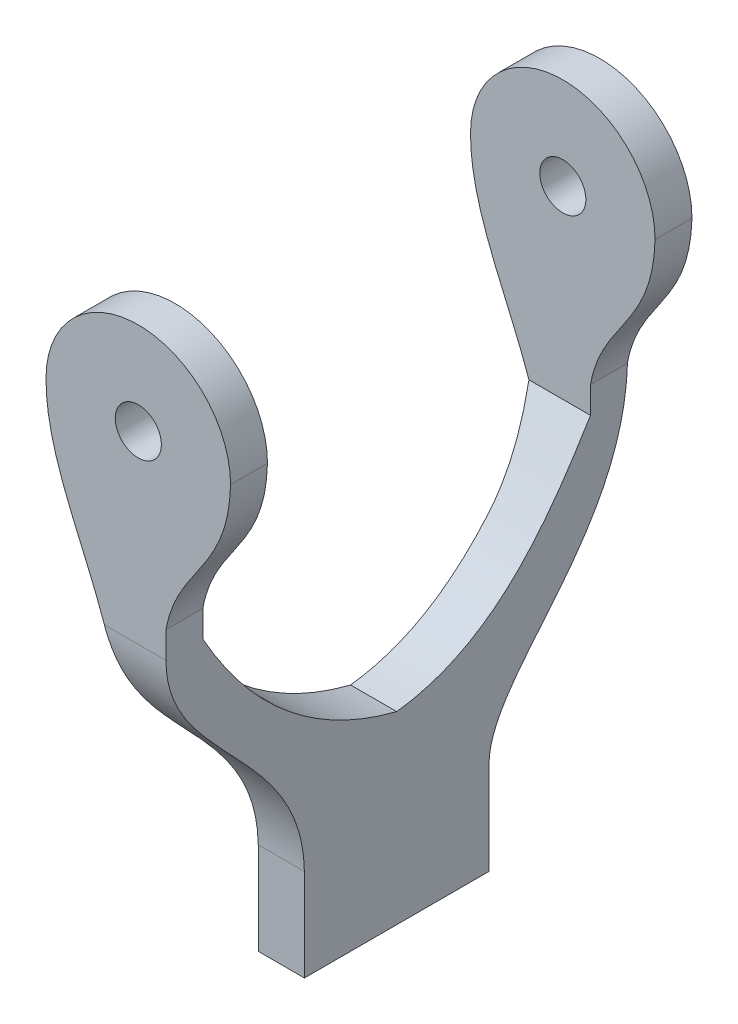
SolidWorks part; units mm, degrees
ref_plane "Plan de face" through (0, 0, 0) normal (0, 0, 1) x (1, 0, 0)
ref_plane "Plan de dessus" through (0, 0, 0) normal (0, 1, 0) x (1, 0, 0)
ref_plane "Plan de droite" through (0, 0, 0) normal (1, 0, 0) x (0, 0, -1)
sketch "Esquisse1" plane through (0, 0, 0) normal (0, 0, 1) x (1, 0, 0)
  line L0 (0, 0) -> (3, 0)
  line L2 (3, 0) -> (-2, 0)
  line L3 (3, 0) -> (3, -57.3)
  line L4 (3, -57.3) -> (-2, -57.3)
  line L5 (-2, 0) -> (-2, -57.3)
  circle A0 centre (0, 0) radius 10
  circle A1 centre (0, 0) radius 2.5
  spline S0 degree 3 poles (10, 0) (9.7605, -8.6814) (4.197, -10.3098) (3, -17.1257) knots 0 0 0 0 1 1 1 1
  spline S1 degree 3 poles (-10, 0) (-10.0381, -9.9152) (-2.1321, -18.0107) (-2, -28.65) knots 0 0 0 0 1 1 1 1
  dimension "D1" = 3
  dimension "D2" = 20
  dimension "D3" = 5
  dimension "D4" = 57.3
  dimension "D5" = 5
extrude "Boss.-Extru.1" add sketch "Esquisse1" along normal blind 50 contours A0 S1 L5 | A0 L5 L4 L3 | S0 A0 L3 | S0 A0 L5 A1 L2 L3 | A1 L5 A0 L3 L2 region at (-0.8796, 2.6387, 0) region at (0.5747, -5.836, 0) region at (5.2237, -10.1125, 0) region at (0.5022, -33.5908, 0) region at (-4.6024, -13.316, 0)
sketch "Esquisse2" plane through (3, 0, 0) normal (1, 0, 0) x (0, 0, -1)
  line L0 (-50, -57.3) -> (-35, -57.3) construction
  line L1 (-50, -57.3) -> (0, -57.3) construction
  line L2 (-35, -37.3) -> (-46, -37.3) construction
  line L3 (-35, -57.3) -> (-15, -57.3)
  line L4 (-35, -57.3) -> (-35, -37.3)
  line L5 (-35, -37.3) -> (-15, -37.3)
  line L6 (-15, -57.3) -> (-15, -37.3)
  line L7 (-50, -17.1257) -> (-50, -57.3) construction
  line L8 (-46, -37.3) -> (-4, -37.3)
  line L16 (-46, -37.3) -> (-4, -37.3)
  line L17 (-46, -37.3) -> (-46, -20)
  line L18 (-46, -20) -> (-4, -20)
  line L19 (-4, -37.3) -> (-4, -20)
  line L20 (-46, -20) -> (-4, -20)
  line L21 (-46, -20) -> (-46, 10)
  line L22 (-46, 10) -> (-4, 10)
  line L23 (-4, -20) -> (-4, 10)
  line L24 (0, -17.1257) -> (0, -57.3) construction
  line L25 (-50, -17.1257) -> (0, -17.1257) construction
  spline S0 degree 3 poles (-46, -20) (-40.7756, -29.3151) (-33.797, -35.0937) (-25, -37.3) knots 0 0 0 0 1 1 1 1
  spline S1 degree 3 poles (-4, -20) (-8.7085, -27.7514) (-14.5376, -36.0464) (-25, -37.3) knots 0 0 0 0 1 1 1 1
  spline S2 degree 3 poles (-35, -47.3) (-35.2327, -34.6195) (-49.9873, -30.3832) (-50, -20) knots 0 0 0 0 1 1 1 1
  spline S3 degree 3 poles (-15, -47.3) (-14.9788, -39.1519) (-0.4328, -32.7021) (0, -17.1257) knots 0 0 0 0 1 1 1 1
  line M14 (0, -57.3) -> (0, -17.1257)
  line M15 (0, -17.1257) -> (-50, -17.1257)
  line M16 (-50, -17.1257) -> (-50, -57.3)
  line M17 (-50, -57.3) -> (0, -57.3)
  dimension "D1" = 15
  dimension "D2" = 20
  dimension "D3" = 20
  dimension "D4" = 11
  dimension "D5" = 17.3
  dimension "D6" = 42
  dimension "D7" = 42
  dimension "D8" = 30
extrude "Enlèv. mat.-Extru.1" cut sketch "Esquisse2" against normal through all both and the other way through all contours S1 L18 S0 | L23 L22 L21 M15 | L18 L23 L21 M15 | L4 S2 L8 L17 M16 M17 | S3 L6 L19 L16 M17 M14 | S3 L16 L19 | L8 S2 L17 region at (3, -45.4307, 43.5103) region at (3, -45.4169, 6.3087) region at (3, -34.5532, 43.5063) region at (3, -34.92, 5.8137) region at (3, -26.7575, 24.8812) region at (3, -3.5628, 25) region at (3, -18.5628, 25)
ref_axis "Axe1" through (0, 0, 71.835) along (0, 0, -1)
